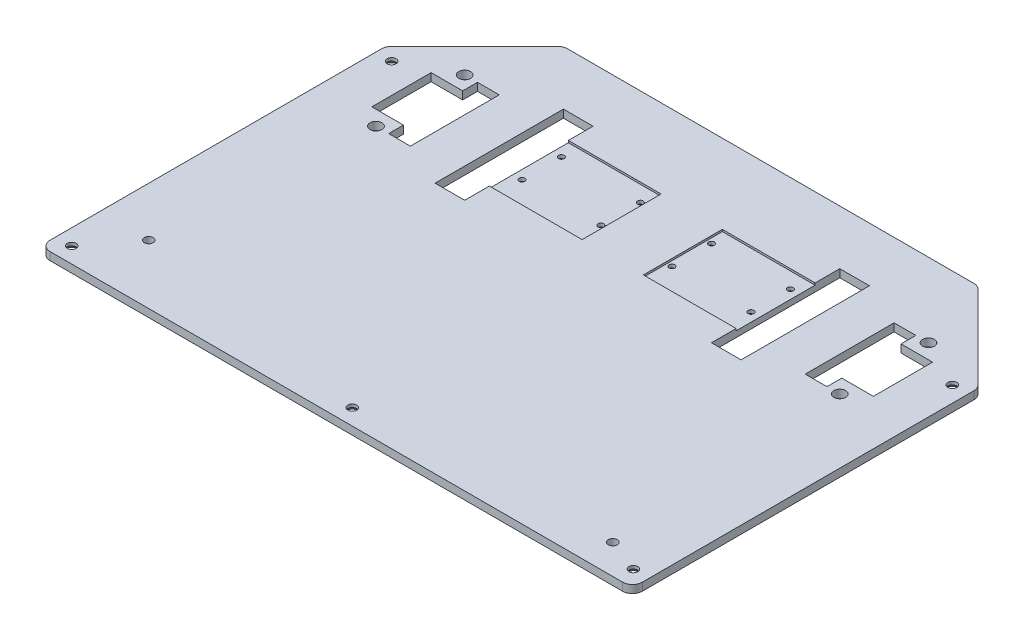
SolidWorks part; units mm, degrees
material "Acier non allié"
ref_plane "Front" through (0, 0, 0) normal (0, 0, 1) x (1, 0, 0)
ref_plane "Top" through (0, 0, 0) normal (0, 1, 0) x (1, 0, 0)
ref_plane "Right" through (0, 0, 0) normal (1, 0, 0) x (0, 0, -1)
sketch "Main scetch" plane through (0, 0, 0) normal (0, 1, 0) x (1, 0, 0)
  line L0 (-150, 0) -> (150, 0)
  line L1 (0, 0) -> (150, 0) construction
  line L2 (0, 0) -> (0, 220) construction
  line L3 (0, 220) -> (150, 220) construction
  line L4 (150, 0) -> (150, 220) construction
  line L5 (150, 0) -> (150, 175)
  line L6 (150, 175) -> (105, 220)
  line L10 (105, 220) -> (-105, 220)
  line L11 (-150, 0) -> (-150, 175)
  line L12 (-150, 175) -> (-105, 220)
  dimension "D1" = 150
  dimension "D2" = 220
  dimension "D3" = 45
  dimension "D4" = 45
extrude "Main extrusion" add sketch "Main scetch" along normal blind 4
fillet "Corner leave" radius 5 6 edges at (-150, 2, 0) (150, 2, -175) (105, 2, -220) (150, 2, 0) (-105, 2, -220) (-150, 2, -175)
sketch "Esquisse2" plane through (0, 4, 0) normal (0, 1, 0) x (1, 0, 0)
  line L0 (-145, 0) -> (145, 0) construction
  line L1 (150, 5) -> (150, 172.9289) construction
  line L2 (148.5355, 176.4645) -> (106.4645, 218.5355) construction
  line L3 (102.9289, 220) -> (-102.9289, 220) construction
  line L4 (-106.4645, 218.5355) -> (-148.5355, 176.4645) construction
  line L5 (-150, 172.9289) -> (-150, 5) construction
  line L6 (-145, 0) -> (145, 0) construction
  line L7 (150, 5) -> (150, 172.9289) construction
  line L8 (148.5355, 176.4645) -> (106.4645, 218.5355) construction
  line L9 (102.9289, 220) -> (-102.9289, 220) construction
  line L10 (-106.4645, 218.5355) -> (-148.5355, 176.4645) construction
  line L11 (-150, 172.9289) -> (-150, 5) construction
  line L12 (0, 0) -> (0, 238.9669) construction
  line L13 (0, 160) -> (165.6987, 160) construction
  line L14 (70, 230.4421) -> (70, 102.0601) construction
  line L15 (62.5, 192.5) -> (77.5, 192.5)
  line L16 (62.5, 192.5) -> (62.5, 127.5)
  line L17 (62.5, 127.5) -> (77.5, 127.5)
  line L18 (77.5, 192.5) -> (77.5, 127.5)
  line L19 (100, 137.5) -> (100, 182.5)
  line L20 (100, 182.5) -> (111, 182.5)
  line L22 (127, 175) -> (127, 145)
  line L23 (100, 137.5) -> (111, 137.5)
  line L35 (111, 182.5) -> (111, 175)
  line L36 (111, 175) -> (127, 175)
  line L37 (111, 137.5) -> (111, 145)
  line L38 (111, 145) -> (127, 145)
  line L39 (-111, 137.5) -> (-111, 145)
  line L40 (-100, 137.5) -> (-111, 137.5)
  line L41 (-100, 137.5) -> (-100, 182.5)
  line L42 (-100, 182.5) -> (-111, 182.5)
  line L43 (-111, 182.5) -> (-111, 175)
  line L44 (-111, 175) -> (-127, 175)
  line L45 (-127, 175) -> (-127, 145)
  line L46 (-111, 145) -> (-127, 145)
  line L47 (-62.5, 127.5) -> (-77.5, 127.5)
  line L48 (-77.5, 192.5) -> (-77.5, 127.5)
  line L49 (-62.5, 192.5) -> (-77.5, 192.5)
  line L50 (-62.5, 192.5) -> (-62.5, 127.5)
  circle A0 centre (117.47, 182.47) radius 3
  circle A1 centre (117.47, 137.53) radius 3
  circle A2 centre (-117.47, 137.53) radius 3
  circle A3 centre (-117.47, 182.47) radius 3
  point P28 (127, 160)
  point P29 (100, 160)
  dimension "D12" = 6
  dimension "D1" = 60
  dimension "D2" = 65
  dimension "D3" = 70
  dimension "D4" = 15
  dimension "D5" = 27
  dimension "D6" = 45
  dimension "D7" = 100
  dimension "D8" = 11
  dimension "D9" = 30
  dimension "D10" = 17.47
  dimension "D11" = 22.47
extrude "Enlèv. mat.-Extru.1" cut sketch "Esquisse2" against normal through all
sketch "Esquisse8" plane through (0, 4, 0) normal (0, 1, 0) x (1, 0, 0)
  line L0 (-150, 172.9289) -> (-150, 5) construction
  line L1 (-145, 0) -> (145, 0) construction
  line L2 (-125, -12.15) -> (-125, 30) construction
  line L3 (150, 5) -> (150, 172.9289) construction
  circle A0 centre (-125, 30) radius 1.5
  circle A1 centre (125, 15) radius 1.5
  circle A2 centre (-125, 12.5) radius 1
  circle A3 centre (-125, 47.5) radius 1
  dimension "D1" = 3
  dimension "D4" = 3
  dimension "D6" = 25
  dimension "D7" = 2
  dimension "D8" = 2
  dimension "D2" = 25
  dimension "D3" = 30
  dimension "D5" = 15
  dimension "D9" = 17.5
  dimension "D10" = 17.5
hole_wizard "Dégagement M41" positions "Esquisse16" profile "Esquisse17" hole size "M4" standard "ISO" end condition through all
sketch "Esquisse16" plane through (0, 4, 0) normal (0, 1, 0) x (1, 0, 0)
  point P0 (-125, 30)
  point P3 (125, 15)
sketch "Esquisse17" plane through (-125, 4, -30) normal (1, 0, 0) x (0, 0, 1)
  line L0 (0, 0) -> (0, 4)
  line L1 (0, 4) -> (2.25, 4)
  line L2 (2.25, 4) -> (2.25, 0)
  line L5 (2.25, 0) -> (0, 0)
  line L11 (0, -6.35) -> (0, 107.95) construction
  dimension "Diamètre du perçage jusqu'au prochain" = 4.5
  dimension "Profondeur du perçage jusqu'au prochain" = 4
sketch "Esquisse18" plane through (0, 4, 0) normal (0, 1, 0) x (1, 0, 0)
  line L0 (-150, 172.9289) -> (-150, 5) construction
  line L1 (-145, 0) -> (145, 0) construction
  line L3 (150, 5) -> (150, 172.9289) construction
  line L4 (0, 0) -> (0, 20.6924) construction
  circle A0 centre (-142, 8) radius 1
  circle A1 centre (-142, 170) radius 1
  circle A4 centre (142, 170) radius 1
  circle A5 centre (142, 8) radius 1
  circle A6 centre (0, 8) radius 1.5
  dimension "D1" = 2
  dimension "D2" = 2
  dimension "D3" = 3
  dimension "D4" = 8
  dimension "D5" = 2
  dimension "D6" = 2
  dimension "D7" = 8
  dimension "D8" = 8
  dimension "D9" = 170
  dimension "D10" = 8
  dimension "D15" = 8
  dimension "D16" = 170
  dimension "D17" = 8
  dimension "D18" = 8
sketch "Esquisse23" plane through (0, 4, 0) normal (0, 1, 0) x (1, 0, 0)
  line L0 (-62.5, 127.5) -> (-62.5, 192.5) construction
  line L1 (-62.5, 180) -> (-15.5, 180)
  line L2 (-62.5, 180) -> (-62.5, 140)
  line L3 (-62.5, 140) -> (-15.5, 140)
  line L4 (-15.5, 180) -> (-15.5, 140)
  line L5 (102.9289, 220) -> (-102.9289, 220) construction
  dimension "D1" = 40
  dimension "D2" = 47
  dimension "D3" = 40
extrude "Enlèv. mat.-Extru.2" cut sketch "Esquisse23" against normal blind 1
sketch "Esquisse24" plane through (0, 3, 0) normal (0, 1, 0) x (1, 0, 0)
  line L0 (-58, 228.7511) -> (-58, 75.2489) construction
  line L1 (-62.5, 180) -> (-62.5, 140) construction
  line L2 (-15.5, 180) -> (-62.5, 180) construction
  line L3 (-18, 126.9657) -> (-18, 195.1017) construction
  line L4 (-58, 172) -> (-9.2469, 172) construction
  line L5 (-58, 152) -> (-13.1999, 152) construction
  circle A0 centre (-58, 172) radius 1
  circle A1 centre (-58, 152) radius 1
  circle A2 centre (-18, 172) radius 1
  circle A3 centre (-18, 152) radius 1
  dimension "D1" = 2
  dimension "D2" = 2
  dimension "D7" = 2
  dimension "D8" = 2
  dimension "D3" = 20
  dimension "D4" = 4.5
  dimension "D5" = 8
  dimension "D6" = 40
extrude "Enlèv. mat.-Extru.3" cut sketch "Esquisse24" against normal through all
hole_wizard "Fraisage pour vis à tête fraisée M2.51" positions "Esquisse27" profile "Esquisse28" countersink size "M2.5" standard "ISO" end condition through all
sketch "Esquisse27" plane through (0, 0, 0) normal (0, -1, 0) x (-1, 0, 0)
  point P0 (18, 172)
  point P3 (58, 172)
  point P6 (58, 152)
  point P9 (18, 152)
sketch "Esquisse28" plane through (-18, 0, -172) normal (1, 0, 0) x (0, 0, -1)
  line L0 (0, 0) -> (0, 4)
  line L1 (0, 4) -> (1.45, 4)
  line L2 (1.45, 4) -> (1.45, 1.3)
  line L3 (1.45, 1.3) -> (2.75, 0)
  line L5 (2.75, 0) -> (0, 0)
  line L6 (-1.45, 1.3) -> (-2.75, 0) construction
  line L11 (0, -6.35) -> (0, 107.95) construction
  dimension "Diamètre du perçage jusqu'au prochain" = 2.9
  dimension "Profondeur du perçage jusqu'au prochain" = 4
  dimension "Diamètre du fraisage entrant" = 5.5
  dimension "Angle du fraisage entrant" = 90
mirror "Symétrie1" about plane through (0, 0, 0) normal (1, 0, 0) of "Enlèv. mat.-Extru.3", "Fraisage pour vis à tête fraisée M2.51", "Enlèv. mat.-Extru.2"
hole_wizard "Fraisage pour vis à tête fraisée M41" positions "Esquisse30" profile "Esquisse31" countersink size "M4" standard "ISO" end condition through all
sketch "Esquisse30" plane through (0, 0, 0) normal (0, -1, 0) x (-1, 0, 0)
  point P0 (-142.0349, 8.4348)
  point P2 (0, 8.1016)
  point P4 (0, 8.1016)
  point P6 (142, 8)
  point P9 (142, 170)
  point P12 (-142, 170)
sketch "Esquisse31" plane through (142.0349, 0, -8.4348) normal (1, 0, 0) x (0, 0, -1)
  line L0 (0, 0) -> (0, 4)
  line L1 (0, 4) -> (2.25, 4)
  line L2 (2.25, 4) -> (2.25, 2.45)
  line L3 (2.25, 2.45) -> (4.7, 0)
  line L5 (4.7, 0) -> (0, 0)
  line L6 (-2.25, 2.45) -> (-4.7, 0) construction
  line L11 (0, -6.35) -> (0, 107.95) construction
  dimension "Diamètre du perçage jusqu'au prochain" = 4.5
  dimension "Profondeur du perçage jusqu'au prochain" = 4
  dimension "Diamètre du fraisage entrant" = 9.4
  dimension "Angle du fraisage entrant" = 90
equation "\"WIDTH\"= 300mm'Total width of the robot"
equation "\"LENGTH\"= 220mm'Total length of the robot"
equation "\"D1@Main scetch\" = \"WIDTH\" / 2"
equation "\"D2@Main scetch\" = \"LENGTH\""
equation "\"CUT_DEPTH\"= 45mm'Depth of the cut on the edges of the plate"
equation "\"D3@Main scetch\" = \"CUT_DEPTH\""
equation "\"D4@Main scetch\" = \"CUT_DEPTH\""
equation "\"Plate_th\"= 3mm'Thickness of the plate"
equation "\"D1\"= \"Plate_th\""
